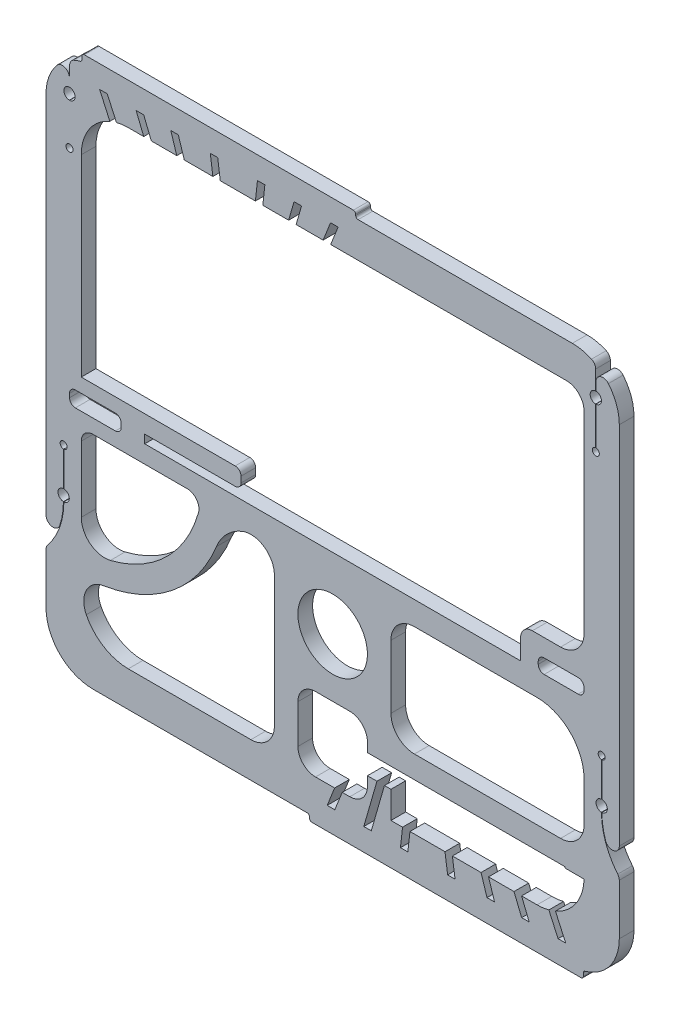
SolidWorks part; units mm, degrees
ref_plane "Front Plane" through (0, 0, 0) normal (0, 0, 1) x (1, 0, 0)
ref_plane "Top Plane" through (0, 0, 0) normal (0, 1, 0) x (1, 0, 0)
ref_plane "Right Plane" through (0, 0, 0) normal (1, 0, 0) x (0, 0, -1)
sketch "Sketch1" plane through (0, 0, 0) normal (0, 0, 1) x (1, 0, 0)
  line L0 (44.642, 21.8842) -> (44.642, 18.0742) construction
  line L1 (-10.1934, 21.8842) -> (51.7832, 21.8842)
  line L2 (-10.1934, 21.8842) -> (-10.1934, -36.406)
  line L3 (-10.1934, -36.406) -> (51.7832, -36.406)
  line L4 (51.7832, 21.8842) -> (51.7832, -36.406)
  line L5 (47.9732, -32.596) -> (-6.3834, -32.596)
  line L6 (47.9732, -32.596) -> (47.9732, 18.0742)
  line L7 (47.9732, 18.0742) -> (-6.3834, 18.0742)
  line L8 (-6.3834, -32.596) -> (-6.3834, 18.0742)
  line L9 (44.642, 19.9792) -> (-35.1587, 19.9792) construction
  line L10 (-6.3834, -31.0517) -> (-10.1934, -31.0517) construction
  line L11 (-8.2884, -31.0517) -> (-8.2884, 6.9585) construction
  line L12 (20.6521, 19.9792) -> (21.1982, 19.9792) construction
  line L14 (3.0779, -32.596) -> (3.0779, -36.406) construction
  line L15 (3.0779, -34.501) -> (37.3423, -34.501) construction
  line L16 (47.9732, -11.8991) -> (47.9732, 12.9942) construction
  line L17 (51.7832, 15.2205) -> (47.9732, 15.2205) construction
  line L18 (49.8782, 15.2205) -> (49.8782, -0.9437) construction
  line L20 (20.9378, -34.501) -> (20.3916, -34.501) construction
  line L21 (-6.3834, 8.0412) -> (-6.3834, -11.8991) construction
  dimension "D1" = 3.81
  dimension "D2" = 3.81
extrude "Boss-Extrude1" add sketch "Sketch1" along normal blind 1.5875
sketch "Sketch2" plane through (0, 0, 0) normal (0, 0, -1) x (-1, 0, 0)
  line L0 (-47.9732, -32.596) -> (-47.9732, 18.0742) construction
  line L1 (-34.8696, 3.2518) -> (6.3834, 3.2518) construction
  line L2 (-47.9732, 3.653) -> (-47.9732, 0.4065) construction
  line L3 (-37.4096, 0.7118) -> (6.3834, 0.7118) construction
  line L4 (6.3834, 3.2518) -> (6.3834, 0.7118) construction
  line L5 (6.3834, 18.0742) -> (6.3834, -32.596) construction
  line L8 (-47.9732, -13.182) -> (-9.1041, -13.182)
  line L9 (-47.9732, -13.182) -> (-47.9732, -10.642)
  line L10 (-47.9732, -10.642) -> (-6.771, -10.642)
  line L11 (1.357, -21.2563) -> (14.2432, -21.2563) construction
  line L12 (6.3834, -23.7963) -> (6.3834, -26.3363)
  line L13 (-47.9732, 13.8154) -> (-47.9732, 11.2754) construction
  line L14 (-41.1149, -10.642) -> (-0.4749, -10.642) construction
  line L15 (-40.2005, -1.1932) -> (-39.5655, -1.1932) construction
  arc A0 (-47.9732, 11.2754) -> (-37.4096, 0.7118) centre (-47.9732, 0.7118) cw construction
  arc A1 (-47.9732, 13.8154) -> (-34.8696, 3.2518) centre (-47.9732, 0.4065) cw construction
  arc A2 (6.3834, -23.7963) -> (-6.771, -10.642) centre (6.3834, -10.642) cw
  arc A3 (-9.1041, -13.182) -> (6.3834, -26.3363) centre (6.3834, -10.642) ccw
  circle A5 centre (1.357, -18.2591) radius 2.9972 construction
  line M5 (-47.9732, -32.596) -> (-47.9732, 18.0742)
  line M7 (6.3834, 18.0742) -> (6.3834, -32.596)
  dimension "D5" = 2.54
  dimension "D1" = 2.54
  dimension "D2" = 2.54
  dimension "D3" = 2.54
  dimension "D4" = 2.54
  dimension "D6" = 2.54
  dimension "D7" = 2.54
  dimension "D8" = 1.905
extrude "Boss-Extrude2" add sketch "Sketch2" against normal up to surface (1.5875 mm away) contours L8 A3 A2 L10 M7 M5 region at (47.4075, -11.912, 0) up to face at (20.7949, -7.2609, 1.5875)
sketch "Sketch3" plane through (0, 0, 0) normal (0, 0, -1) x (-1, 0, 0)
  line L0 (-47.9732, -7.1876) -> (-41.1149, -7.1876)
  line L1 (-47.9732, -10.642) -> (-47.9732, 18.0742) construction
  line L2 (-47.9732, -10.642) -> (-6.771, -10.642) construction
  line L3 (-41.1149, -7.1876) -> (-41.1149, -10.642)
  line L5 (-41.1149, -10.642) -> (-43.0199, -10.642)
  line L6 (-43.0199, -10.642) -> (-43.0199, -9.0926)
  line L7 (-43.0199, -9.0926) -> (-47.9732, -9.0926)
  line L8 (-47.9732, -9.0926) -> (-47.9732, -7.1876)
  line L19 (-0.4749, -9.7276) -> (-41.1149, -9.7276) construction
  line L21 (-41.1149, -9.7276) -> (-41.1149, -10.642) construction
  dimension "D1" = 1.905
  dimension "D2" = 1.905
  dimension "D3" = 2.54
extrude "Boss-Extrude3" add sketch "Sketch3" against normal up to surface (1.5875 mm away) up to face at (18.535, -2.3312, 1.5875)
fillet "Fillet1" radius 5.08 4 edges at (51.7832, -36.406, 0.7937) (-10.1934, -36.406, 0.7937) (-10.1934, 21.8842, 0.7937) (51.7832, 21.8842, 0.7937)
fillet "Fillet2" radius 5.08 6 edges at (9.1041, -13.182, 0.7937) (47.9732, -13.182, 0.7937) (47.9732, -32.596, 0.7937) (-6.3834, -32.596, 0.7937) (-6.3834, 18.0742, 0.7937) (6.771, -10.642, 0.7937)
fillet "Fillet3" radius 2.54 3 edges at (47.9732, -7.1876, 0.7938) (-6.3834, -26.3363, 0.7937) (-6.3834, -23.7963, 0.7937)
sketch "Sketch5" plane through (0, 0, 0) normal (0, 0, -1) x (-1, 0, 0)
  line L1 (-27.0941, -13.182) -> (-14.4957, -13.182)
  line L2 (-27.0941, -13.182) -> (-27.0941, -32.596)
  line L3 (-27.0941, -32.596) -> (-14.4957, -32.596)
  line L4 (-14.4957, -13.182) -> (-14.4957, -32.596)
  line L5 (1.3034, -32.596) -> (-42.8932, -32.596) construction
  line L6 (-24.5541, -18.2972) -> (-27.0941, -18.2972) construction
  line L7 (-42.8932, -13.182) -> (-12.943, -13.182) construction
  line L9 (-17.0357, -18.2972) -> (-14.4957, -18.2972) construction
  circle A1 centre (-20.7949, -18.2972) radius 3.7592 construction
  dimension "D1" = 2.54
extrude "Boss-Extrude4" add sketch "Sketch5" against normal up to surface (1.5875 mm away) up to face at (45.4966, -9.8673, 1.5875)
sketch "Sketch6" plane through (0, 0, 0) normal (0, 0, -1) x (-1, 0, 0)
  circle A0 centre (-20.7949, -18.2972) radius 3.7592 construction
  circle A1 centre (-20.7949, -18.2972) radius 3.7592
extrude "Cut-Extrude2" cut sketch "Sketch6" against normal up to surface (1.5875 mm away) up to face at (5.503, -23.566, 1.5875)
sketch "Sketch7" plane through (0, 0, 0) normal (0, 0, -1) x (-1, 0, 0)
  line L0 (-27.0941, -13.182) -> (-27.0941, -32.596) construction
  line L1 (-24.5541, -24.5964) -> (-17.0357, -24.5964)
  line L2 (-24.5541, -24.5964) -> (-24.5541, -32.596)
  line L3 (-24.5541, -32.596) -> (-17.0357, -32.596)
  line L4 (-17.0357, -24.5964) -> (-17.0357, -32.596)
  line L5 (-14.4957, -32.596) -> (-14.4957, -13.182) construction
  line L6 (1.3034, -32.596) -> (-14.4957, -32.596) construction
  line L7 (-20.7949, -22.0564) -> (-6.5424, -22.0564) construction
  line L8 (-20.7949, -22.0564) -> (-20.7949, -21.3452) construction
  circle A0 centre (-20.7949, -18.2972) radius 3.7592 construction
  dimension "D1" = 2.54
  dimension "D2" = 2.54
  dimension "D3" = 2.54
extrude "Cut-Extrude3" cut sketch "Sketch7" against normal up to surface (1.5875 mm away) up to face at (24.5541, -18.2972, 1.5875)
fillet "Fillet5" radius 1.905 4 edges at (24.5541, -32.596, 0.7937) (17.0357, -32.596, 0.7938) (17.0357, -24.5964, 0.7938) (24.5541, -24.5964, 0.7938)
sketch "Sketch8" plane through (0, 0, 0) normal (0, 0, -1) x (-1, 0, 0)
  line L0 (-47.9732, -27.516) -> (-47.9732, -18.262) construction
  line L1 (-47.9732, -25.103) -> (-27.0941, -25.103)
  line L2 (-47.9732, -25.103) -> (-47.9732, -27.643)
  line L3 (-47.9732, -27.643) -> (-27.0941, -27.643)
  line L4 (-27.0941, -25.103) -> (-27.0941, -27.643)
  line L5 (-27.0941, -13.182) -> (-27.0941, -32.596) construction
  line L6 (-45.7916, -27.643) -> (-20.3916, -27.643) construction
  dimension "D1" = 2.54
extrude "Boss-Extrude5" add sketch "Sketch8" against normal up to surface (1.5875 mm away) up to face at (20.7949, -28.5962, 1.5875)
fillet "Fillet6" radius 2.54 5 edges at (27.0941, -13.182, 0.7937) (14.4957, -13.182, 0.7937) (14.4957, -32.596, 0.7937) (27.0941, -25.103, 0.7937) (47.9732, -25.103, 0.7937)
sketch "Sketch4" plane through (0, 0, 0) normal (0, 0, -1) x (-1, 0, 0)
  line L32 (4.2018, 13.1212) -> (4.2018, 15.0262)
  line L33 (4.2018, 15.0262) -> (1.9539, 15.0262)
  line L34 (1.9539, 15.0262) -> (4.2018, 19.9792)
  line L35 (4.2018, 19.9792) -> (3.6556, 19.9792)
  line L36 (3.6556, 19.9792) -> (1.4078, 15.0262)
  line L37 (1.4078, 15.0262) -> (-1.7417, 15.0262)
  line L38 (-1.7417, 15.0262) -> (0.2648, 19.9792)
  line L39 (0.2648, 19.9792) -> (-0.2814, 19.9792)
  line L40 (-0.2814, 19.9792) -> (-2.2879, 15.0262)
  line L41 (-2.2879, 15.0262) -> (-5.0437, 15.0262)
  line L42 (-5.0437, 15.0262) -> (-3.469, 19.9792)
  line L43 (-3.469, 19.9792) -> (-4.0152, 19.9792)
  line L44 (-4.0152, 19.9792) -> (-5.5899, 15.0262)
  line L45 (-5.5899, 15.0262) -> (-8.3965, 15.0262)
  line L46 (-8.3965, 15.0262) -> (-7.7108, 19.9792)
  line L47 (-7.7108, 19.9792) -> (-8.257, 19.9792)
  line L48 (-8.257, 19.9792) -> (-8.9427, 15.0262)
  line L49 (-8.9427, 15.0262) -> (-12.2319, 15.0262)
  line L50 (-12.2319, 15.0262) -> (-12.7781, 19.9792)
  line L51 (-12.7781, 19.9792) -> (-13.3242, 19.9792)
  line L52 (-13.3242, 19.9792) -> (-12.7781, 15.0262)
  line L53 (-12.7781, 15.0262) -> (-15.2926, 15.0262)
  line L54 (-15.2926, 15.0262) -> (-16.7151, 19.9792)
  line L55 (-16.7151, 19.9792) -> (-17.2612, 19.9792)
  line L56 (-17.2612, 19.9792) -> (-15.8388, 15.0262)
  line L57 (-15.8388, 15.0262) -> (-18.6963, 15.0262)
  line L58 (-18.6963, 15.0262) -> (-20.6521, 19.9792)
  line L59 (-20.6521, 19.9792) -> (-21.1982, 19.9792)
  line L60 (-21.1982, 19.9792) -> (-19.2425, 15.0262)
  line L61 (-19.2425, 15.0262) -> (-21.1982, 15.0262)
  line L62 (-21.1982, 15.0262) -> (-21.1982, 13.1212)
  line L63 (-21.1982, 13.1212) -> (4.2018, 13.1212)
  line L64 (4.2018, 13.1212) -> (4.2018, 15.0262) construction
  line L65 (4.2018, 15.0262) -> (1.9539, 15.0262) construction
  line L66 (1.9539, 15.0262) -> (4.2018, 19.9792) construction
  line L67 (4.2018, 19.9792) -> (3.6556, 19.9792) construction
  line L68 (3.6556, 19.9792) -> (1.4078, 15.0262) construction
  line L69 (1.4078, 15.0262) -> (-1.7417, 15.0262) construction
  line L70 (-1.7417, 15.0262) -> (0.2648, 19.9792) construction
  line L71 (0.2648, 19.9792) -> (-0.2814, 19.9792) construction
  line L72 (-0.2814, 19.9792) -> (-2.2879, 15.0262) construction
  line L73 (-2.2879, 15.0262) -> (-5.0437, 15.0262) construction
  line L74 (-5.0437, 15.0262) -> (-3.469, 19.9792) construction
  line L75 (-3.469, 19.9792) -> (-4.0152, 19.9792) construction
  line L76 (-4.0152, 19.9792) -> (-5.5899, 15.0262) construction
  line L77 (-5.5899, 15.0262) -> (-8.3965, 15.0262) construction
  line L78 (-8.3965, 15.0262) -> (-7.7108, 19.9792) construction
  line L79 (-7.7108, 19.9792) -> (-8.257, 19.9792) construction
  line L80 (-8.257, 19.9792) -> (-8.9427, 15.0262) construction
  line L81 (-8.9427, 15.0262) -> (-12.2319, 15.0262) construction
  line L82 (-12.2319, 15.0262) -> (-12.7781, 19.9792) construction
  line L83 (-12.7781, 19.9792) -> (-13.3242, 19.9792) construction
  line L84 (-13.3242, 19.9792) -> (-12.7781, 15.0262) construction
  line L85 (-12.7781, 15.0262) -> (-15.2926, 15.0262) construction
  line L86 (-15.2926, 15.0262) -> (-16.7151, 19.9792) construction
  line L87 (-16.7151, 19.9792) -> (-17.2612, 19.9792) construction
  line L88 (-17.2612, 19.9792) -> (-15.8388, 15.0262) construction
  line L89 (-15.8388, 15.0262) -> (-18.6963, 15.0262) construction
  line L90 (-18.6963, 15.0262) -> (-20.6521, 19.9792) construction
  line L91 (-20.6521, 19.9792) -> (-21.1982, 19.9792) construction
  line L92 (-21.1982, 19.9792) -> (-19.2425, 15.0262) construction
  line L93 (-19.2425, 15.0262) -> (-21.1982, 15.0262) construction
  line L94 (-21.1982, 15.0262) -> (-21.1982, 13.1212) construction
  line L95 (-21.1982, 13.1212) -> (4.2018, 13.1212) construction
  line L96 (-45.7916, -27.643) -> (-45.7916, -29.548)
  line L97 (-45.7916, -29.548) -> (-43.5438, -29.548)
  line L98 (-43.5438, -29.548) -> (-45.7916, -34.501)
  line L99 (-45.7916, -34.501) -> (-45.2455, -34.501)
  line L100 (-45.2455, -34.501) -> (-42.9976, -29.548)
  line L101 (-42.9976, -29.548) -> (-39.8482, -29.548)
  line L102 (-39.8482, -29.548) -> (-41.8546, -34.501)
  line L103 (-41.8546, -34.501) -> (-41.3085, -34.501)
  line L104 (-41.3085, -34.501) -> (-39.302, -29.548)
  line L105 (-39.302, -29.548) -> (-36.5462, -29.548)
  line L106 (-36.5462, -29.548) -> (-38.1208, -34.501)
  line L107 (-38.1208, -34.501) -> (-37.5747, -34.501)
  line L108 (-37.5747, -34.501) -> (-36, -29.548)
  line L109 (-36, -29.548) -> (-33.1934, -29.548)
  line L110 (-33.1934, -29.548) -> (-33.879, -34.501)
  line L111 (-33.879, -34.501) -> (-33.3329, -34.501)
  line L112 (-33.3329, -34.501) -> (-32.6472, -29.548)
  line L113 (-32.6472, -29.548) -> (-29.358, -29.548)
  line L114 (-29.358, -29.548) -> (-28.8118, -34.501)
  line L115 (-28.8118, -34.501) -> (-28.2656, -34.501)
  line L116 (-28.2656, -34.501) -> (-28.8118, -29.548)
  line L117 (-28.8118, -29.548) -> (-26.2973, -29.548)
  line L118 (-26.2973, -29.548) -> (-24.8748, -34.501)
  line L119 (-24.8748, -34.501) -> (-24.3286, -34.501)
  line L120 (-24.3286, -34.501) -> (-25.7511, -29.548)
  line L121 (-25.7511, -29.548) -> (-22.8935, -29.548)
  line L122 (-22.8935, -29.548) -> (-20.9378, -34.501)
  line L123 (-20.9378, -34.501) -> (-20.3916, -34.501)
  line L124 (-20.3916, -34.501) -> (-22.3474, -29.548)
  line L125 (-22.3474, -29.548) -> (-20.3916, -29.548)
  line L126 (-20.3916, -29.548) -> (-20.3916, -27.643)
  line L127 (-20.3916, -27.643) -> (-45.7916, -27.643)
  line L128 (-45.7916, -27.643) -> (-45.7916, -29.548) construction
  line L129 (-45.7916, -29.548) -> (-43.5438, -29.548) construction
  line L130 (-43.5438, -29.548) -> (-45.7916, -34.501) construction
  line L131 (-45.7916, -34.501) -> (-45.2455, -34.501) construction
  line L132 (-45.2455, -34.501) -> (-42.9976, -29.548) construction
  line L133 (-42.9976, -29.548) -> (-39.8482, -29.548) construction
  line L134 (-39.8482, -29.548) -> (-41.8546, -34.501) construction
  line L135 (-41.8546, -34.501) -> (-41.3085, -34.501) construction
  line L136 (-41.3085, -34.501) -> (-39.302, -29.548) construction
  line L137 (-39.302, -29.548) -> (-36.5462, -29.548) construction
  line L138 (-36.5462, -29.548) -> (-38.1208, -34.501) construction
  line L139 (-38.1208, -34.501) -> (-37.5747, -34.501) construction
  line L140 (-37.5747, -34.501) -> (-36, -29.548) construction
  line L141 (-36, -29.548) -> (-33.1934, -29.548) construction
  line L142 (-33.1934, -29.548) -> (-33.879, -34.501) construction
  line L143 (-33.879, -34.501) -> (-33.3329, -34.501) construction
  line L144 (-33.3329, -34.501) -> (-32.6472, -29.548) construction
  line L145 (-32.6472, -29.548) -> (-29.358, -29.548) construction
  line L146 (-29.358, -29.548) -> (-28.8118, -34.501) construction
  line L147 (-28.8118, -34.501) -> (-28.2656, -34.501) construction
  line L148 (-28.2656, -34.501) -> (-28.8118, -29.548) construction
  line L149 (-28.8118, -29.548) -> (-26.2973, -29.548) construction
  line L150 (-26.2973, -29.548) -> (-24.8748, -34.501) construction
  line L151 (-24.8748, -34.501) -> (-24.3286, -34.501) construction
  line L152 (-24.3286, -34.501) -> (-25.7511, -29.548) construction
  line L153 (-25.7511, -29.548) -> (-22.8935, -29.548) construction
  line L154 (-22.8935, -29.548) -> (-20.9378, -34.501) construction
  line L155 (-20.9378, -34.501) -> (-20.3916, -34.501) construction
  line L156 (-20.3916, -34.501) -> (-22.3474, -29.548) construction
  line L157 (-22.3474, -29.548) -> (-20.3916, -29.548) construction
  line L158 (-20.3916, -29.548) -> (-20.3916, -27.643) construction
  line L159 (-20.3916, -27.643) -> (-45.7916, -27.643) construction
  line L263 (4.3288, 12.9942) -> (4.3288, 15.1532)
  line L264 (4.3288, 15.1532) -> (2.151, 15.1532)
  line L265 (2.151, 15.1532) -> (4.3989, 20.1062)
  line L266 (4.3989, 20.1062) -> (3.5738, 20.1062)
  line L267 (3.5738, 20.1062) -> (1.3259, 15.1532)
  line L268 (1.3259, 15.1532) -> (-1.5532, 15.1532)
  line L269 (-1.5532, 15.1532) -> (0.4532, 20.1062)
  line L270 (0.4532, 20.1062) -> (-0.367, 20.1062)
  line L271 (-0.367, 20.1062) -> (-2.3735, 15.1532)
  line L272 (-2.3735, 15.1532) -> (-4.8701, 15.1532)
  line L273 (-4.8701, 15.1532) -> (-3.2954, 20.1062)
  line L274 (-3.2954, 20.1062) -> (-4.1081, 20.1062)
  line L275 (-4.1081, 20.1062) -> (-5.6828, 15.1532)
  line L276 (-5.6828, 15.1532) -> (-8.2507, 15.1532)
  line L277 (-8.2507, 15.1532) -> (-7.565, 20.1062)
  line L278 (-7.565, 20.1062) -> (-8.3676, 20.1062)
  line L279 (-8.3676, 20.1062) -> (-9.0533, 15.1532)
  line L280 (-9.0533, 15.1532) -> (-12.1181, 15.1532)
  line L281 (-12.1181, 15.1532) -> (-12.6643, 20.1062)
  line L282 (-12.6643, 20.1062) -> (-13.466, 20.1062)
  line L283 (-13.466, 20.1062) -> (-12.9198, 15.1532)
  line L284 (-12.9198, 15.1532) -> (-15.1969, 15.1532)
  line L285 (-15.1969, 15.1532) -> (-16.6194, 20.1062)
  line L286 (-16.6194, 20.1062) -> (-17.4298, 20.1062)
  line L287 (-17.4298, 20.1062) -> (-16.0074, 15.1532)
  line L288 (-16.0074, 15.1532) -> (-18.6099, 15.1532)
  line L289 (-18.6099, 15.1532) -> (-20.5657, 20.1062)
  line L290 (-20.5657, 20.1062) -> (-21.3849, 20.1062)
  line L291 (-21.3849, 20.1062) -> (-19.4292, 15.1532)
  line L292 (-19.4292, 15.1532) -> (-21.3252, 15.1532)
  line L293 (-21.3252, 15.1532) -> (-21.3252, 12.9942)
  line L294 (-21.3252, 12.9942) -> (4.3288, 12.9942)
  line L295 (-45.9186, -27.516) -> (-45.9186, -29.675)
  line L296 (-45.9186, -29.675) -> (-43.7409, -29.675)
  line L297 (-43.7409, -29.675) -> (-45.9887, -34.628)
  line L298 (-45.9887, -34.628) -> (-45.1636, -34.628)
  line L299 (-45.1636, -34.628) -> (-42.9158, -29.675)
  line L300 (-42.9158, -29.675) -> (-40.0367, -29.675)
  line L301 (-40.0367, -29.675) -> (-42.0431, -34.628)
  line L302 (-42.0431, -34.628) -> (-41.2229, -34.628)
  line L303 (-41.2229, -34.628) -> (-39.2164, -29.675)
  line L304 (-39.2164, -29.675) -> (-36.7198, -29.675)
  line L305 (-36.7198, -29.675) -> (-38.2945, -34.628)
  line L306 (-38.2945, -34.628) -> (-37.4818, -34.628)
  line L307 (-37.4818, -34.628) -> (-35.9071, -29.675)
  line L308 (-35.9071, -29.675) -> (-33.3392, -29.675)
  line L309 (-33.3392, -29.675) -> (-34.0248, -34.628)
  line L310 (-34.0248, -34.628) -> (-33.2222, -34.628)
  line L311 (-33.2222, -34.628) -> (-32.5366, -29.675)
  line L312 (-32.5366, -29.675) -> (-29.4717, -29.675)
  line L313 (-29.4717, -29.675) -> (-28.9256, -34.628)
  line L314 (-28.9256, -34.628) -> (-28.1239, -34.628)
  line L315 (-28.1239, -34.628) -> (-28.67, -29.675)
  line L316 (-28.67, -29.675) -> (-26.3929, -29.675)
  line L317 (-26.3929, -29.675) -> (-24.9705, -34.628)
  line L318 (-24.9705, -34.628) -> (-24.16, -34.628)
  line L319 (-24.16, -34.628) -> (-25.5825, -29.675)
  line L320 (-25.5825, -29.675) -> (-22.9799, -29.675)
  line L321 (-22.9799, -29.675) -> (-21.0242, -34.628)
  line L322 (-21.0242, -34.628) -> (-20.205, -34.628)
  line L323 (-20.205, -34.628) -> (-22.1607, -29.675)
  line L324 (-22.1607, -29.675) -> (-20.2646, -29.675)
  line L325 (-20.2646, -29.675) -> (-20.2646, -27.516)
  line L326 (-20.2646, -27.516) -> (-45.9186, -27.516)
  dimension "D1" = 0
  dimension "D2" = 0
  dimension "D3" = 0.127
  dimension "D4" = 0.127
extrude "Cut-Extrude1" cut sketch "Sketch4" against normal up to surface (1.5875 mm away) up to face at (37.2819, -19.3942, 1.5875)
sketch "Sketch9" plane through (0, 0, 0) normal (0, 0, -1) x (-1, 0, 0)
  circle A0 centre (-49.2432, 18.0742) radius 0.6096 construction
  circle A1 centre (7.6534, 18.0742) radius 0.6096 construction
  circle A2 centre (8.2884, -19.8366) radius 0.6096 construction
  circle A3 centre (-49.8782, -19.8366) radius 0.6096 construction
  circle A4 centre (-49.2432, 18.0742) radius 0.6096
  circle A5 centre (7.6534, 18.0742) radius 0.6096
  circle A6 centre (8.2884, -19.8366) radius 0.6096
  circle A7 centre (-49.8782, -19.8366) radius 0.6096
extrude "Cut-Extrude4" cut sketch "Sketch9" against normal up to surface (1.5875 mm away) up to face at (31.4097, -31.792, 1.5875)
sketch "Sketch10" plane through (0, 0, 1.5875) normal (0, 0, 1) x (1, 0, 0)
  line L0 (-7.6407, 18.6837) -> (-7.6407, 20.7449) construction
  line L1 (-7.6407, 13.375) -> (-7.6407, 17.4647) construction
  line L2 (-7.6661, 17.4647) -> (-7.6661, 13.375) construction
  line L3 (-7.6661, 19.5715) -> (-7.6661, 18.6837) construction
  line L4 (-7.6407, 18.6837) -> (-7.6407, 20.7449)
  line L5 (-7.6407, 13.375) -> (-7.6407, 17.4647)
  line L6 (-7.6661, 17.4647) -> (-7.6661, 13.375)
  line L7 (-7.6661, 19.5715) -> (-7.6661, 18.6837)
  line L8 (49.2305, 18.6837) -> (49.2305, 20.7449) construction
  line L9 (49.2305, 13.375) -> (49.2305, 17.4647) construction
  line L10 (49.2559, 17.4647) -> (49.2559, 13.375) construction
  line L11 (49.2559, 19.5715) -> (49.2559, 18.6837) construction
  line L12 (49.2305, 18.6837) -> (49.2305, 20.7449)
  line L13 (49.2305, 13.375) -> (49.2305, 17.4647)
  line L14 (49.2559, 17.4647) -> (49.2559, 13.375)
  line L15 (49.2559, 19.5715) -> (49.2559, 18.6837)
  line L16 (49.8909, -15.5181) -> (49.8909, -19.2271) construction
  line L17 (49.8655, -15.5181) -> (49.8655, -19.2271) construction
  line L18 (49.8909, -15.5181) -> (49.8909, -19.2271)
  line L19 (49.8655, -15.5181) -> (49.8655, -19.2271)
  line L20 (-8.2757, -15.5181) -> (-8.2757, -19.2271) construction
  line L21 (-8.3011, -15.5181) -> (-8.3011, -19.2271) construction
  line L22 (-8.2757, -15.5181) -> (-8.2757, -19.2271)
  line L23 (-8.3011, -15.5181) -> (-8.3011, -19.2271)
  line L24 (51.7832, -31.326) -> (51.7832, 16.8042) construction
  line L25 (51.7832, -25.8445) -> (51.7832, -22.639)
  line L26 (-10.1934, 16.8042) -> (-10.1934, -31.326) construction
  line L27 (-10.1934, -22.639) -> (-10.1934, -25.8445)
  arc A1 (-7.1902, 21.4403) -> (-7.6407, 20.7449) centre (-6.8787, 20.7449) ccw construction
  arc A2 (-7.6661, 13.375) -> (-7.6407, 13.375) centre (-7.6534, 12.9942) ccw construction
  arc A3 (-7.6661, 19.5715) -> (-9.013, 20.0598) centre (-8.4281, 19.5715) ccw construction
  arc A4 (-5.1134, 21.8842) -> (-10.1934, 16.8042) centre (-5.1134, 16.8042) ccw construction
  arc A5 (-7.1902, 21.4403) -> (-7.6407, 20.7449) centre (-6.8787, 20.7449) ccw
  arc A6 (-7.6661, 13.375) -> (-7.6407, 13.375) centre (-7.6534, 12.9942) ccw
  arc A7 (-7.6661, 19.5715) -> (-9.013, 20.0598) centre (-8.4281, 19.5715) ccw
  arc A8 (-7.1902, 21.4403) -> (-9.013, 20.0598) centre (-5.1134, 16.8042) ccw
  circle A9 centre (-7.6534, 18.0742) radius 0.6096 construction
  arc A10 (-7.6407, 18.6837) -> (-7.6661, 18.6837) centre (-7.6534, 18.0742) ccw
  arc A11 (-7.6661, 17.4647) -> (-7.6407, 17.4647) centre (-7.6534, 18.0742) ccw
  arc A12 (49.2305, 20.7449) -> (48.7801, 21.4403) centre (48.4685, 20.7449) ccw construction
  arc A13 (49.2305, 13.375) -> (49.2559, 13.375) centre (49.2432, 12.9942) ccw construction
  arc A14 (50.6029, 20.0598) -> (49.2559, 19.5715) centre (50.0179, 19.5715) ccw construction
  arc A15 (49.2305, 20.7449) -> (48.7801, 21.4403) centre (48.4685, 20.7449) ccw
  arc A16 (49.2305, 13.375) -> (49.2559, 13.375) centre (49.2432, 12.9942) ccw
  arc A17 (50.6029, 20.0598) -> (49.2559, 19.5715) centre (50.0179, 19.5715) ccw
  arc A18 (49.8909, -15.5181) -> (49.8655, -15.5181) centre (49.8782, -15.1373) ccw construction
  arc A19 (49.9036, -20.4457) -> (50.2983, -22.8798) centre (57.6041, -20.4462) ccw construction
  arc A20 (49.8528, -20.4457) -> (51.6105, -25.3613) centre (57.6041, -20.4462) ccw construction
  arc A21 (50.2983, -22.8798) -> (51.7832, -22.639) centre (51.0212, -22.639) ccw construction
  arc A22 (51.7832, -25.8445) -> (51.6105, -25.3613) centre (51.0212, -25.8445) ccw construction
  arc A23 (49.8909, -15.5181) -> (49.8655, -15.5181) centre (49.8782, -15.1373) ccw
  arc A24 (49.9036, -20.4457) -> (50.2983, -22.8798) centre (57.6041, -20.4462) ccw
  arc A25 (49.8528, -20.4457) -> (51.6105, -25.3613) centre (57.6041, -20.4462) ccw
  arc A26 (50.2983, -22.8798) -> (51.7832, -22.639) centre (51.0212, -22.639) ccw
  arc A27 (51.7832, -25.8445) -> (51.6105, -25.3613) centre (51.0212, -25.8445) ccw
  arc A28 (-10.1934, -22.639) -> (-8.7084, -22.8798) centre (-9.4314, -22.639) ccw construction
  arc A29 (-10.0206, -25.3613) -> (-8.263, -20.4457) centre (-16.0142, -20.4462) ccw construction
  arc A30 (-8.7084, -22.8798) -> (-8.3138, -20.4457) centre (-16.0142, -20.4462) ccw construction
  arc A31 (-8.2757, -15.5181) -> (-8.3011, -15.5181) centre (-8.2884, -15.1373) ccw construction
  arc A32 (-10.1934, -22.639) -> (-8.7084, -22.8798) centre (-9.4314, -22.639) ccw
  arc A33 (-10.0206, -25.3613) -> (-8.263, -20.4457) centre (-16.0142, -20.4462) ccw
  arc A34 (-8.7084, -22.8798) -> (-8.3138, -20.4457) centre (-16.0142, -20.4462) ccw
  arc A35 (-8.2757, -15.5181) -> (-8.3011, -15.5181) centre (-8.2884, -15.1373) ccw
  arc A36 (51.7832, 16.8042) -> (46.7032, 21.8842) centre (46.7032, 16.8042) ccw construction
  arc A37 (50.6029, 20.0598) -> (48.7801, 21.4403) centre (46.7032, 16.8042) ccw
  circle A38 centre (49.2432, 18.0742) radius 0.6096 construction
  arc A39 (49.2559, 18.6837) -> (49.2305, 18.6837) centre (49.2432, 18.0742) ccw
  arc A40 (49.2305, 17.4647) -> (49.2559, 17.4647) centre (49.2432, 18.0742) ccw
  circle A41 centre (49.8782, -19.8366) radius 0.6096 construction
  arc A42 (49.8909, -19.2271) -> (49.8655, -19.2271) centre (49.8782, -19.8366) ccw
  arc A43 (49.8528, -20.4457) -> (49.9036, -20.4457) centre (49.8782, -19.8366) ccw
  circle A44 centre (-8.2884, -19.8366) radius 0.6096 construction
  arc A45 (-8.2757, -19.2271) -> (-8.3011, -19.2271) centre (-8.2884, -19.8366) ccw
  arc A46 (-8.3138, -20.4457) -> (-8.263, -20.4457) centre (-8.2884, -19.8366) ccw
  arc A47 (-10.0206, -25.3613) -> (-10.1934, -25.8445) centre (-9.4314, -25.8445) ccw construction
  arc A48 (-10.0206, -25.3613) -> (-10.1934, -25.8445) centre (-9.4314, -25.8445) ccw
extrude "Slots for carbon" cut sketch "Sketch10" against normal through all
fillet "Fillet7" radius 1.905 1 edges at (47.9732, 18.0742, 0.7937)
sketch "Sketch11" plane through (0, 0, 0) normal (0, 0, -1) x (-1, 0, 0)
  line L1 (-0.4749, -9.7276) -> (-0.4749, -10.642) construction
  line L2 (-7.1635, -12.547) -> (6.3834, -12.547)
  line L3 (6.3834, 12.9942) -> (6.3834, -20.9479) construction
  line L4 (6.3834, -12.547) -> (6.3834, -7.8226)
  line L5 (-0.4749, -10.642) -> (-11.129, -10.642)
  line L7 (-0.4749, -9.7276) -> (-0.4749, -10.642)
  line L8 (-0.4749, -9.7276) -> (-10.8889, -9.7276)
  line L9 (-10.8889, -9.7276) -> (-10.8889, -7.8226)
  line L10 (-10.8889, -7.8226) -> (6.3834, -7.8226)
  arc A0 (-6.2502, -14.3067) -> (-11.129, -10.642) centre (-11.129, -15.722) ccw construction
  arc A1 (-7.1635, -12.547) -> (-11.129, -10.642) centre (-11.129, -15.722) ccw
  dimension "D1" = 1.905
  dimension "D2" = 1.905
  dimension "D3" = 10.414
extrude "Boss-Extrude6" add sketch "Sketch11" against normal up to surface (1.5875 mm away) up to face at (20.7949, -2.3483, 1.5875)
fillet "Fillet8" radius 1.27 3 edges at (41.1149, -7.1876, 0.7938) (-6.3834, -12.547, 0.7937) (7.1635, -12.547, 0.7937)
sketch "Sketch12" plane through (0, 0, 0) normal (0, 0, -1) x (-1, 0, 0)
  line L0 (3.1233, -7.8226) -> (3.1233, -9.3466) construction
  line L1 (2.0651, -9.3466) -> (7.6534, -9.3466)
  line L2 (2.0651, -9.3466) -> (2.0651, -11.023)
  line L3 (2.0651, -11.023) -> (7.6534, -11.023)
  line L4 (7.6534, -9.3466) -> (7.6534, -11.023)
  line L5 (6.3834, -7.8226) -> (-10.8889, -7.8226) construction
  line L6 (2.0651, -10.1848) -> (-0.4749, -10.1848) construction
  line L7 (3.1233, -11.023) -> (3.1233, -12.547) construction
  line L8 (-5.0715, -12.547) -> (5.1134, -12.547) construction
  line L9 (-0.4749, -9.7276) -> (-0.4749, -10.642) construction
  line L10 (7.6534, -10.1848) -> (10.1934, -10.1848) construction
  line L11 (10.1934, 16.8042) -> (10.1934, -22.639) construction
  dimension "D1" = 1.524
  dimension "D2" = 2.54
extrude "Cut-Extrude5" cut sketch "Sketch12" against normal through all
fillet "Fillet9" radius 0.635 10 edges at (47.9732, -10.642, 0.7937) (47.9732, -9.0926, 0.7938) (43.0199, -9.0926, 0.7938) (43.0199, -10.642, 0.7938) (-7.6534, -11.023, 0.7937) (-7.6534, -9.3466, 0.7938) (-2.0651, -11.023, 0.7938) (-2.0651, -9.3466, 0.7938) (10.8889, -9.7276, 0.7937) (10.8889, -7.8226, 0.7937)
sketch "Sketch13" plane through (0, 0, 0) normal (0, 0, -1) x (-1, 0, 0)
  line L0 (-46.7032, 21.8842) -> (5.1134, 21.8842) construction
  line L1 (-23.2899, 21.8842) -> (5.1134, 21.8842)
  line L2 (-23.2899, 21.8842) -> (-23.2899, 22.5192)
  line L3 (-23.2899, 22.5192) -> (6.3039, 22.5192)
  line L4 (6.3039, 21.7427) -> (6.3039, 22.5192)
  line L5 (5.1134, -36.406) -> (-46.7032, -36.406) construction
  line L6 (-18.3, -36.406) -> (-46.7032, -36.406)
  line L7 (-18.3, -36.406) -> (-18.3, -37.041)
  line L8 (-18.3, -37.041) -> (-47.8937, -37.041)
  line L9 (-47.8937, -36.2645) -> (-47.8937, -37.041)
  arc A0 (7.1902, 21.4403) -> (5.1134, 21.8842) centre (5.1134, 16.8042) ccw construction
  arc A1 (6.3039, 21.7427) -> (5.1134, 21.8842) centre (5.1134, 16.8042) ccw
  arc A2 (-51.7832, -31.326) -> (-46.7032, -36.406) centre (-46.7032, -31.326) ccw construction
  arc A3 (-47.8937, -36.2645) -> (-46.7032, -36.406) centre (-46.7032, -31.326) ccw
  dimension "D1" = 0.635
  dimension "D2" = 1.905
  dimension "D3" = 1.905
  dimension "D4" = 0.635
  dimension "D5" = 1.905
  dimension "D6" = 1.905
extrude "Boss-Extrude7" add sketch "Sketch13" against normal up to surface (1.5875 mm away) up to face at (-4.8592, -10.1848, 1.5875)
fillet "Fillet10" radius 0.254 8 edges at (47.8937, -36.2645, 0.7937) (47.8937, -37.041, 0.7937) (18.3, -37.041, 0.7937) (18.3, -36.406, 0.7937) (23.2899, 21.8842, 0.7937) (23.2899, 22.5192, 0.7937) (-6.3039, 22.5192, 0.7937) (-6.3039, 21.7427, 0.7937)
